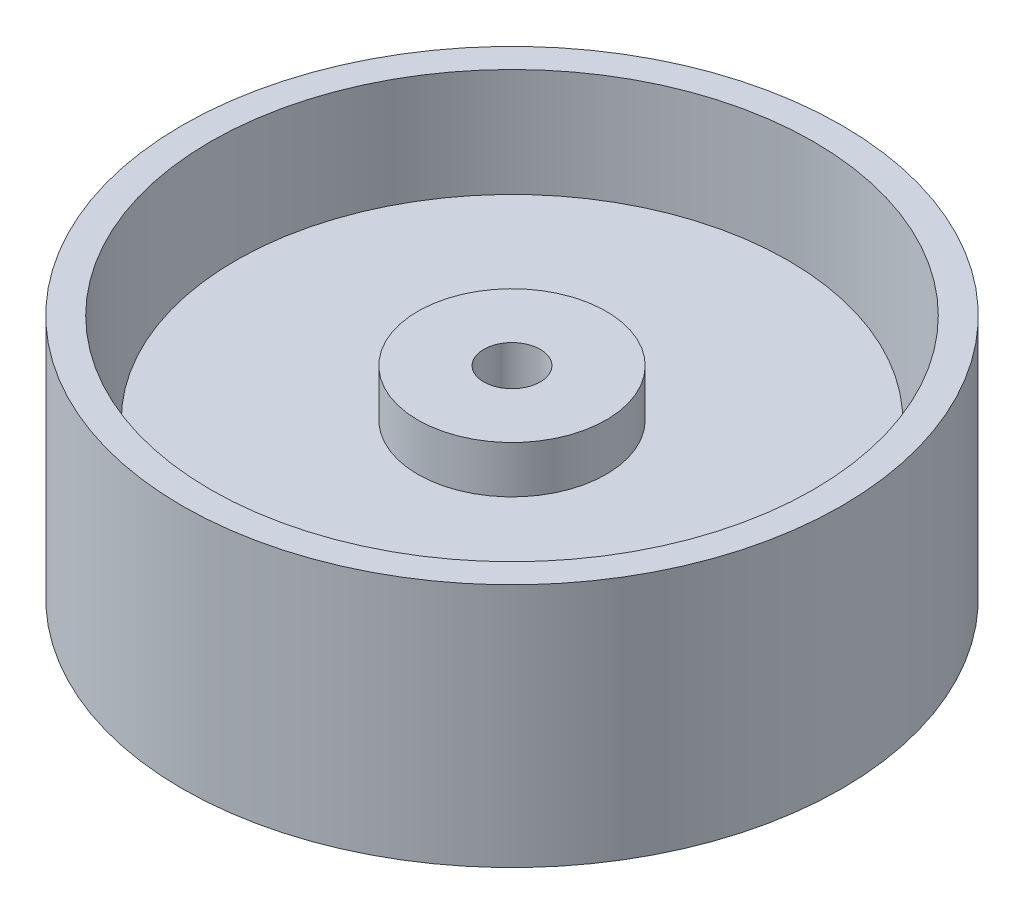
SolidWorks part; units mm, degrees
material "ColorFabb woodFILL"
ref_plane "Front Plane" through (0, 0, 0) normal (0, 0, 1) x (1, 0, 0)
ref_plane "Top Plane" through (0, 0, 0) normal (0, 1, 0) x (1, 0, 0)
ref_plane "Right Plane" through (0, 0, 0) normal (1, 0, 0) x (0, 0, -1)
sketch "Volume Knob" plane through (0, 0, 0) normal (0, 1, 0) x (1, 0, 0)
  line L1 (2.5981, 1.5) -> (-2.5981, 1.5)
  circle A0 centre (0, 0) radius 35
  circle A1 centre (0, 0) radius 20.9
  circle A2 centre (0, 0) radius 32
  circle A3 centre (0, 0) radius 3
  circle A4 centre (0, 0) radius 5.5
  circle A5 centre (0, 0) radius 27.5
  circle A6 centre (0, 0) radius 29.33
  circle A7 centre (0, 0) radius 10
  point P11 (0, 1)
  point P12 (0, 1.5)
extrude "Knob Top" add sketch "Volume Knob" along normal blind 3.5 contours A0
extrude "Knob Walls" add sketch "Volume Knob<3>" along normal blind 26 contours A0 | A2
sketch "Volume Knob<3>" plane through (0, 0, 0) normal (0, 1, 0) x (1, 0, 0) same geometry as "Volume Knob"
extrude "Knob Shaft Keyway" add sketch "Volume Knob<4>" along normal blind 10 from surface contours L1 A3 region at (0, 0, -2.1151) starting at face at (0, 3.5, 32)
sketch "Volume Knob<4>" plane through (0, 0, 0) normal (0, 1, 0) x (1, 0, 0) same geometry as "Volume Knob"
extrude "Knob Damepning Extension (top)" add sketch "Volume Knob<8>" along normal blind 12.9 from surface contours A6 | A3 starting at face at (0, 3.5, 32)
sketch "Volume Knob<8>" plane through (0, 0, 0) normal (0, 1, 0) x (1, 0, 0) same geometry as "Volume Knob"
extrude "Knob Shaft Support" add sketch "Volume Knob<11>" along normal blind 5 from surface contours A3 | A7 starting at face at (0, 16.4, 29.33)
sketch "Volume Knob<11>" plane through (0, 0, 0) normal (0, 1, 0) x (1, 0, 0) same geometry as "Volume Knob"
